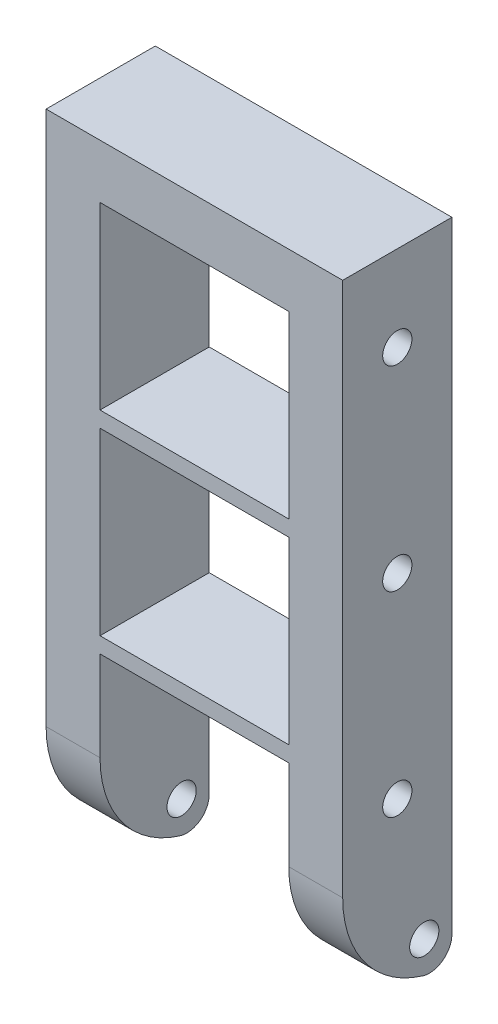
SolidWorks part; units mm, degrees
material "PBT General Purpose"
ref_plane "Front Plane" through (0, 0, 0) normal (0, 0, 1) x (1, 0, 0)
ref_plane "Top Plane" through (0, 0, 0) normal (0, 1, 0) x (1, 0, 0)
ref_plane "Right Plane" through (0, 0, 0) normal (1, 0, 0) x (0, 0, -1)
sketch "Sketch2" plane through (0, 0, 0) normal (0, 0, 1) x (1, 0, 0)
  line L0 (-33, 0) -> (33, 0)
  line L1 (33, 0) -> (33, -144)
  line L2 (33, -144) -> (21, -144)
  line L3 (21, -144) -> (21, -99)
  line L4 (21, -99) -> (-21, -99)
  line L5 (-21, -99) -> (-21, -144)
  line L6 (-21, -144) -> (-33, -144)
  line L7 (-33, -144) -> (-33, 0)
  line L8 (-21, -99) -> (-21, -95.5) construction
  line L9 (-21, -52) -> (21, -52)
  line L10 (-21, -52) -> (-21, -12)
  line L11 (-21, -12) -> (21, -12)
  line L12 (21, -52) -> (21, -12)
  line L13 (-21, -95.5) -> (21, -95.5)
  line L14 (-21, -95.5) -> (-21, -55.5)
  line L15 (-21, -55.5) -> (21, -55.5)
  line L16 (21, -95.5) -> (21, -55.5)
  line L17 (-21, -55.5) -> (-21, -52) construction
  line L18 (21, -52) -> (21, -55.5) construction
  line L19 (21, -95.5) -> (21, -99) construction
  dimension "D1" = 12
  dimension "D2" = 42
  dimension "D3" = 45
  dimension "D4" = 43.5
  dimension "D5" = 43.5
  dimension "D6" = 12
  dimension "D7" = 3.5
  dimension "D8" = 3.5
extrude "Boss-Extrude1" add sketch "Sketch2" along normal mid plane 24.3 contours L7 L0 L1 L2 L3 L4 L5 L6 | L10 L11 L12 L9 | L14 L15 L16 L13
sketch "Sketch3" plane through (0, 0, 0) normal (1, 0, 0) x (0, 0, -1)
  line L0 (-12.15, 0) -> (12.15, 0) construction
  circle A2 centre (0, -106) radius 3.25
  circle A3 centre (0, -62.5) radius 3.25
  circle A4 centre (0, -19) radius 3.25
  circle A5 centre (6, -136) radius 3.25
  dimension "D4" = 43.5
  dimension "D1" = 6.5
  dimension "D2" = 6.5
  dimension "D3" = 43.5
  dimension "D5" = 19
  dimension "D6" = 30
  dimension "D7" = 6
extrude "Cut-Extrude1" cut sketch "Sketch3" against normal through all both and the other way through all
fillet "Fillet1" radius 25 2 edges at (27, -144, 12.15) (-27, -144, 12.15)
fillet "Fillet2" radius 5 2 edges at (-27, -144, -12.15) (27, -144, -12.15)
equation "\"frisbee spacing\"= 43.5"
equation "\"D4@Sketch2\"=\"frisbee spacing\""
equation "\"D5@Sketch2\"=\"frisbee spacing\""
equation "\"D4@Sketch3\"=\"frisbee spacing\""
equation "\"D3@Sketch3\"=\"frisbee spacing\""
